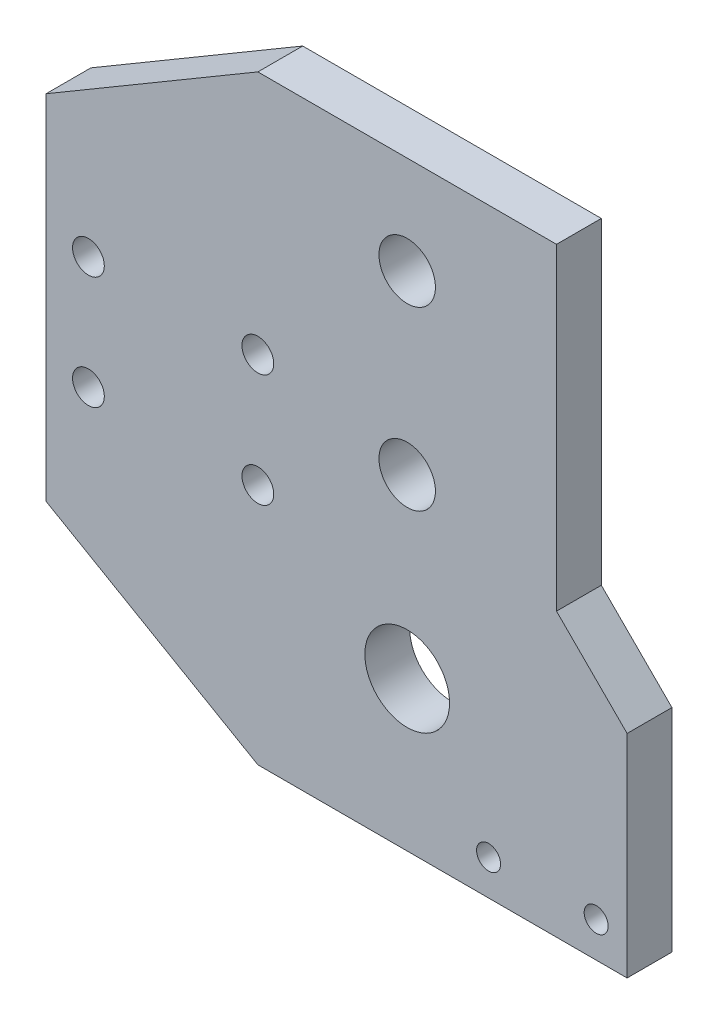
SolidWorks part; units mm, degrees
material "6061 Alloy"
ref_plane "Front Plane" through (0, 0, 0) normal (0, 0, 1) x (1, 0, 0)
ref_plane "Top Plane" through (0, 0, 0) normal (0, 1, 0) x (1, 0, 0)
ref_plane "Right Plane" through (0, 0, 0) normal (1, 0, 0) x (0, 0, -1)
sketch "Sketch2" plane through (0, 0, 0) normal (0, 0, 1) x (1, 0, 0)
  line L0 (0, 0) -> (0, -21.15) construction
  line L1 (-21.15, -21.15) -> (21.15, -21.15)
  line L2 (-21.15, -21.15) -> (-21.15, 63.85)
  line L3 (-21.15, 63.85) -> (21.15, 63.85)
  line L4 (21.15, -21.15) -> (21.15, 63.85)
  circle A0 centre (0, 0) radius 6
  circle A1 centre (0, 25) radius 4
  circle A2 centre (0, 50) radius 4
  dimension "D1" = 12
  dimension "D5" = 25
  dimension "D7" = 8
  dimension "D2" = 21.15
  dimension "D3" = 42.3
  dimension "D4" = 85
  dimension "D6" = 25
extrude "Boss-Extrude1" add sketch "Sketch2" along normal blind 6.35
sketch "Sketch8" plane through (0, 0, 6.35) normal (0, 0, 1) x (1, 0, 0)
  line L0 (-21.15, -21.15) -> (-51.15, -3.8295)
  line L1 (-51.15, -3.8295) -> (-51.15, 46.1705)
  line L2 (-51.15, 46.1705) -> (-21.15, 63.85)
  line L3 (-21.15, 63.85) -> (-21.15, -21.15) construction
  line L4 (-21.15, 63.85) -> (-21.15, -21.15)
  dimension "D2" = 60
  dimension "D3" = 30
  dimension "D4" = 50
extrude "Boss-Extrude2" add sketch "Sketch8" against normal up to surface (6.35 mm away) up to face at (4, 25, 0)
sketch "Sketch9" plane through (0, 0, 6.35) normal (0, 0, 1) x (1, 0, 0)
  line L0 (-51.15, 21.1705) -> (-33.15, 21.1705) construction
  line L1 (-51.15, 46.1705) -> (-51.15, -3.8295) construction
  line L3 (-45.15, 13.1705) -> (-21.15, 13.1705) construction
  line L4 (-45.15, 13.1705) -> (-45.15, 29.1705) construction
  line L5 (-45.15, 29.1705) -> (-21.15, 29.1705) construction
  line L6 (-21.15, 13.1705) -> (-21.15, 29.1705) construction
  line L7 (-45.15, 13.1705) -> (-21.15, 29.1705) construction
  line L8 (-45.15, 29.1705) -> (-21.15, 13.1705) construction
  point P4 (-21.15, 29.1705)
  point P5 (-45.15, 13.1705)
  point P6 (-45.15, 29.1705)
  point P7 (-21.15, 13.1705)
  dimension "D1" = 18
  dimension "D2" = 16
  dimension "D3" = 24
hole_wizard "M4 Clearance Hole1" positions "Sketch9" profile "Sketch10" hole size "M4" standard "ANSI Metric" end condition through all
sketch "Sketch10" plane through (-21.15, 13.1705, 6.35) normal (1, 0, 0) x (0, -1, 0)
  line L0 (0, 0) -> (0, 6.35)
  line L1 (0, 6.35) -> (2.25, 6.35)
  line L2 (2.25, 6.35) -> (2.25, 0)
  line L5 (2.25, 0) -> (0, 0)
  line L11 (0, -6.35) -> (0, 107.95) construction
  dimension "Thru Hole Dia." = 4.5
  dimension "Thru Hole Depth" = 6.35
sketch "Sketch11" plane through (0, 0, 6.35) normal (0, 0, 1) x (1, 0, 0)
  line L0 (21.15, -21.15) -> (31.15, -21.15)
  line L1 (31.15, -21.15) -> (31.15, 8.85)
  line L2 (31.15, 8.85) -> (21.15, 18.85)
  line L3 (21.15, -21.15) -> (21.15, 63.85) construction
  line L4 (21.15, 18.85) -> (21.15, -21.15)
  dimension "D1" = 10
  dimension "D2" = 30
  dimension "D3" = 45
extrude "Boss-Extrude3" add sketch "Sketch11" against normal up to surface (6.35 mm away) up to face at (-18.9, 29.1705, 0)
sketch "Sketch14" plane through (0, 0, 6.35) normal (0, 0, 1) x (1, 0, 0)
  line L0 (11.53, -16.15) -> (26.77, -16.15) construction
  line L2 (-21.15, -21.15) -> (31.15, -21.15) construction
  line L3 (19.15, -16.15) -> (19.15, -21.15) construction
  line L5 (31.15, -21.15) -> (31.15, 8.85) construction
  point P0 (11.53, -16.15)
  point P1 (26.77, -16.15)
  dimension "D1" = 15.24
  dimension "D2" = 12
  dimension "D3" = 5
hole_wizard "M3 Clearance Hole2" positions "Sketch14" profile "Sketch15" hole size "M3" standard "ANSI Metric" end condition through all
sketch "Sketch15" plane through (11.53, -16.15, 6.35) normal (1, 0, 0) x (0, -1, 0)
  line L0 (0, 0) -> (0, 6.35)
  line L1 (0, 6.35) -> (1.7, 6.35)
  line L2 (1.7, 6.35) -> (1.7, 0)
  line L5 (1.7, 0) -> (0, 0)
  line L11 (0, -6.35) -> (0, 107.95) construction
  dimension "Thru Hole Dia." = 3.4
  dimension "Thru Hole Depth" = 6.35
sketch "Sketch3" plane through (31.15, 0, 0) normal (-1, 0, 0) x (0, 0, 1)
  line L0 (6.35, -6) -> (6.35, 6) construction
  line L1 (6.35, 21) -> (6.35, 29) construction
  line L2 (6.35, 46) -> (6.35, 54) construction
  line L3 (6.35, -6) -> (6.35, 6) construction
  line L4 (6.35, 21) -> (6.35, 29) construction
  line L5 (6.35, 46) -> (6.35, 54) construction
  line L6 (3.175, 63.85) -> (3.175, -21.15) construction
  line L9 (6.35, 0) -> (3.175, 0) construction
  line L10 (6.35, 25) -> (3.175, 25) construction
  line L11 (6.35, 50) -> (3.175, 50) construction
  line L12 (6.35, -21.15) -> (0, -21.15) construction
  line L13 (6.35, 63.85) -> (0, 63.85) construction
  point P13 (3.175, 0)
  point P16 (3.175, 25)
  point P18 (3.175, 50)
  point P26 (3.175, 63.85)
